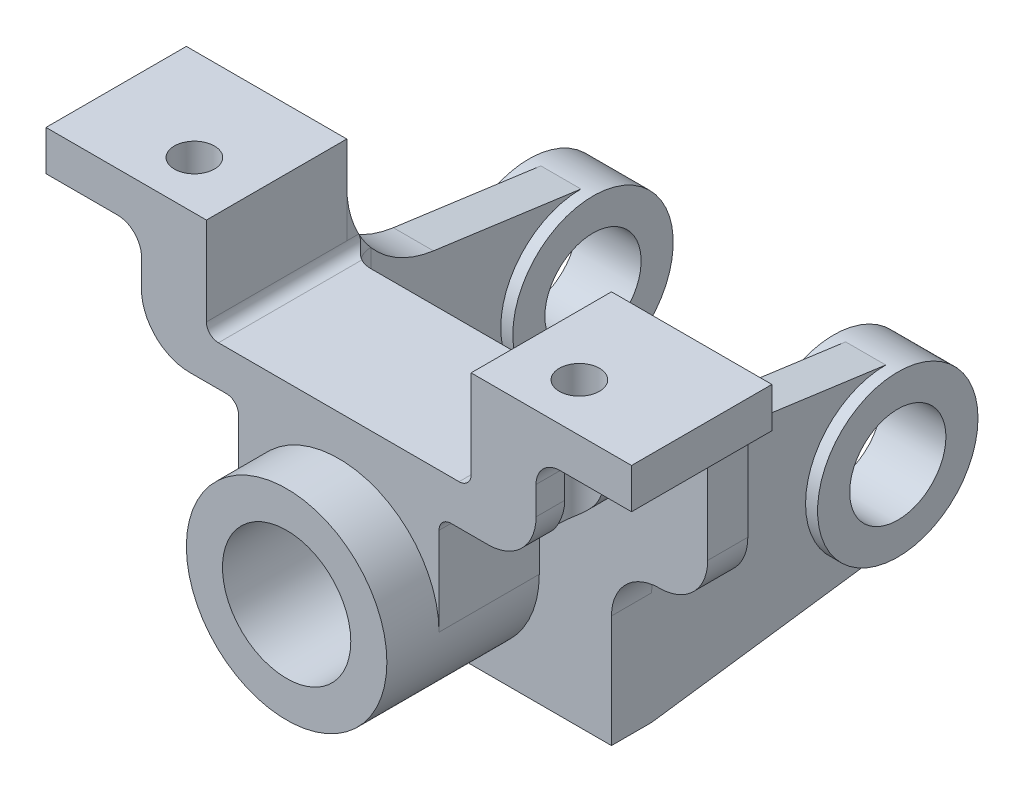
SolidWorks part; units mm, degrees
ref_plane "Front Plane" through (0, 0, 0) normal (0, 0, 1) x (1, 0, 0)
ref_plane "Top Plane" through (0, 0, 0) normal (0, 1, 0) x (1, 0, 0)
ref_plane "Right Plane" through (0, 0, 0) normal (1, 0, 0) x (0, 0, -1)
sketch "Sketch1" plane through (0, 0, 0) normal (0, 0, 1) x (1, 0, 0)
  line L0 (0, 28) -> (0, 0)
  line L1 (0, 0) -> (86, 0)
  line L2 (86, 0) -> (86, 28)
  line L3 (110, 52) -> (110, 72)
  line L4 (116, 78) -> (116, 88)
  line L5 (116, 88) -> (76, 88)
  line L6 (76, 88) -> (76, 66)
  line L7 (43, 0) -> (43, 91.3532) construction
  line L8 (10, 88) -> (10, 66)
  line L9 (-30, 88) -> (10, 88)
  line L10 (-30, 78) -> (-30, 88)
  line L11 (-24, 52) -> (-24, 72)
  line L12 (13, 63) -> (73, 63)
  arc A0 (86, 28) -> (98, 40) centre (98, 28) cw
  arc A1 (98, 40) -> (110, 52) centre (98, 52) ccw
  arc A2 (110, 72) -> (116, 78) centre (116, 72) cw
  arc A3 (76, 66) -> (73, 63) centre (73, 66) cw
  arc A4 (10, 66) -> (13, 63) centre (13, 66) ccw
  arc A5 (-24, 72) -> (-30, 78) centre (-30, 72) ccw
  arc A6 (-12, 40) -> (-24, 52) centre (-12, 52) cw
  arc A7 (0, 28) -> (-12, 40) centre (-12, 28) ccw
  dimension "D4" = 12
  dimension "D6" = 12
  dimension "D10" = 6
  dimension "D16" = 3
  dimension "D2" = 86
  dimension "D3" = 28
  dimension "D5" = 40
  dimension "D7" = 24
  dimension "D8" = 20
  dimension "D9" = 110
  dimension "D11" = 116
  dimension "D12" = 10
  dimension "D13" = 116
  dimension "D14" = 40
  dimension "D15" = 22
  dimension "D17" = 3
extrude "Boss-Extrude1" add sketch "Sketch1" along normal blind 10
sketch "Sketch2" plane through (0, 0, 10) normal (0, 0, 1) x (1, 0, 0)
  line L0 (-30, 88) -> (-30, 78) construction
  line L1 (10, 88) -> (-30, 88) construction
  line L2 (10, 66) -> (10, 88) construction
  line L3 (73, 63) -> (13, 63) construction
  line L4 (76, 88) -> (76, 66) construction
  line L5 (116, 88) -> (76, 88) construction
  line L6 (116, 78) -> (116, 88) construction
  line L7 (-30, 88) -> (-30, 78)
  line L8 (10, 88) -> (-30, 88)
  line L9 (10, 66) -> (10, 88)
  line L10 (73, 63) -> (13, 63)
  line L11 (76, 88) -> (76, 66)
  line L12 (116, 88) -> (76, 88)
  line L13 (116, 78) -> (116, 88)
  line L14 (-30, 78) -> (-12.2, 78)
  line L15 (-6.2, 72) -> (-6.2, 65)
  line L16 (5.8, 53) -> (15, 53)
  line L17 (18, 50) -> (18, 28)
  line L18 (43, 63) -> (43, 0) construction
  line L19 (0, 0) -> (86, 0) construction
  line L20 (68, 50) -> (68, 28)
  line L21 (80.2, 53) -> (71, 53)
  line L22 (92.2, 72) -> (92.2, 65)
  line L23 (116, 78) -> (98.2, 78)
  arc A0 (10, 66) -> (13, 63) centre (13, 66) ccw construction
  arc A1 (73, 63) -> (76, 66) centre (73, 66) ccw construction
  arc A2 (10, 66) -> (13, 63) centre (13, 66) ccw
  arc A3 (73, 63) -> (76, 66) centre (73, 66) ccw
  arc A4 (-6.2, 72) -> (-12.2, 78) centre (-12.2, 72) ccw
  arc A5 (-6.2, 65) -> (5.8, 53) centre (5.8, 65) ccw
  arc A6 (71, 53) -> (68, 50) centre (71, 50) ccw
  arc A7 (15, 53) -> (18, 50) centre (15, 50) cw
  arc A8 (92.2, 65) -> (80.2, 53) centre (80.2, 65) cw
  arc A9 (92.2, 72) -> (98.2, 78) centre (98.2, 72) cw
  arc A10 (68, 28) -> (18, 28) centre (43, 28) cw
  dimension "D2" = 6
  dimension "D5" = 12
  dimension "D9" = 3
  dimension "D7" = 3
  dimension "D12" = 25
  dimension "D1" = 17.8
  dimension "D3" = 6
  dimension "D4" = 7
  dimension "D6" = 25
  dimension "9.2" = 9.2
  dimension "D8" = 10
  dimension "D10" = 22
  dimension "D11" = 48
extrude "Boss-Extrude2" add sketch "Sketch2" along normal blind 25
sketch "Sketch3" plane through (0, 0, 35) normal (0, 0, 1) x (1, 0, 0)
  circle A2 centre (43, 28) radius 25
  dimension "D1" = 50
  dimension "D2" = 43
  dimension "D3" = 28
extrude "Boss-Extrude3" add sketch "Sketch3" along normal blind 13
sketch "Sketch4" plane through (0, 0, 48) normal (0, 0, 1) x (1, 0, 0)
  circle A0 centre (43, 28) radius 16
  dimension "D1" = 32
extrude "Cut-Extrude1" cut sketch "Sketch4" against normal blind 81
sketch "Sketch5" plane through (0, 88, 0) normal (0, 1, 0) x (1, 0, 0)
  line L2 (10, 0) -> (-30, 0) construction
  line L3 (43, -35) -> (43, 0) construction
  line L4 (73, -35) -> (13, -35) construction
  line L5 (73, 0) -> (13, 0) construction
  line L6 (13, -35) -> (13, 0) construction
  circle A0 centre (-5, -23) radius 5
  circle A1 centre (91, -23) radius 5
  dimension "D1" = 10
  dimension "D3" = 23
  dimension "D2" = 18
extrude "Cut-Extrude4" cut sketch "Sketch5" against normal up to next
sketch "Sketch12" plane through (86, 0, 0) normal (1, 0, 0) x (0, 0, -1)
  line L0 (0, 0) -> (0, 56)
  line L1 (0, 52) -> (0, 72) construction
  line L2 (0, 56) -> (58.3946, 48)
  line L3 (0, 0) -> (58.3946, 8)
  arc A0 (58.3946, 8) -> (58.3946, 48) centre (58.3946, 28) ccw
  dimension "D2" = 58.94
  dimension "25" = 40
  dimension "D1" = 56
  dimension "D3" = 58.94
extrude "Boss-Extrude8" add sketch "Sketch12" against normal blind 10
sketch "Sketch13" plane through (0, 0, 0) normal (-1, 0, 0) x (0, 0, 1)
  line L0 (0, 0) -> (-58.3946, 8)
  line L1 (-58.3946, 48) -> (0, 56)
  line L2 (0, 56) -> (0, 0)
  arc A0 (-58.3946, 8) -> (-58.3946, 48) centre (-58.3946, 28) cw
  arc A1 (-58.3946, 48) -> (-58.3946, 8) centre (-58.3946, 28) ccw construction
  dimension "D1" = 58.94
extrude "Boss-Extrude9" add sketch "Sketch13" against normal blind 10
fillet "Fillet4" radius 25 2 edges at (81, 56, 0) (5, 56, 0)
fillet "Fillet6" radius 6 2 edges at (10, 33, 0)
sketch "Sketch14" plane through (0, 0, 0) normal (-1, 0, 0) x (0, 0, 1)
  circle A0 centre (-58.3946, 28) radius 20
extrude "Boss-Extrude10" add sketch "Sketch14" along normal blind 3 and the other way blind 13
sketch "Sketch16" plane through (86, 0, 0) normal (1, 0, 0) x (0, 0, -1)
  circle A0 centre (58.3946, 28) radius 20
extrude "Boss-Extrude11" add sketch "Sketch16" along normal blind 3 and the other way blind 13
sketch "Sketch17" plane through (89, 0, 0) normal (1, 0, 0) x (0, 0, -1)
  circle A0 centre (58.3946, 28) radius 12
  dimension "D1" = 24
extrude "Cut-Extrude5" cut sketch "Sketch17" against normal through all
